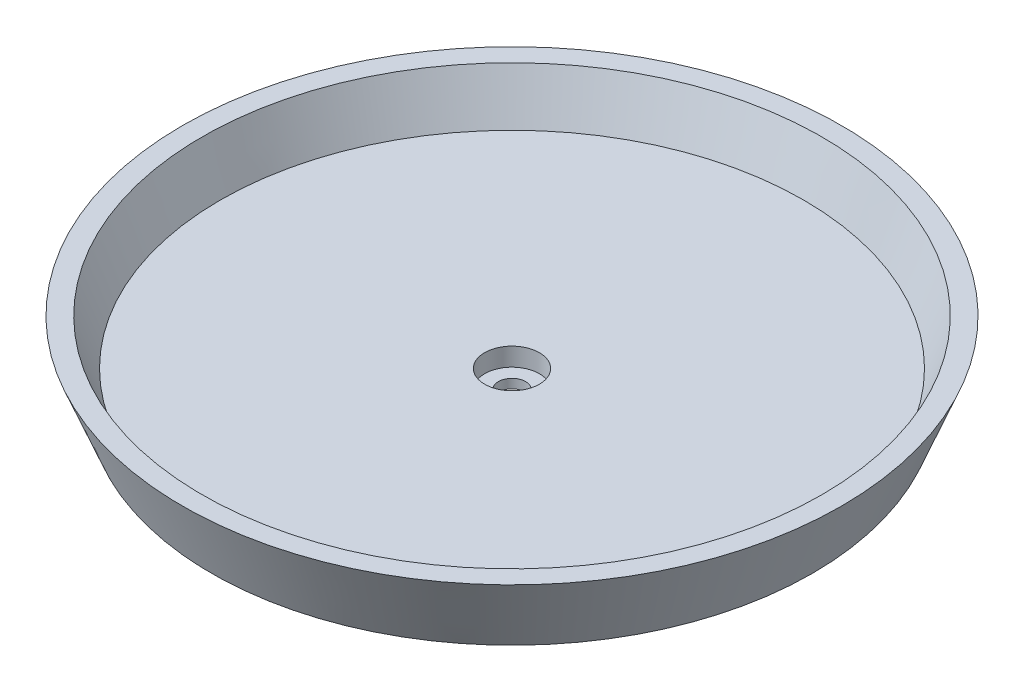
SolidWorks part; units mm, degrees
ref_plane "前视基准面" through (0, 0, 0) normal (0, 0, 1) x (1, 0, 0)
ref_plane "上视基准面" through (0, 0, 0) normal (0, 1, 0) x (1, 0, 0)
ref_plane "右视基准面" through (0, 0, 0) normal (1, 0, 0) x (0, 0, -1)
sketch "草图1" plane through (0, 0, 0) normal (0, 0, 1) x (1, 0, 0)
  line L0 (-50.5774, 13.4762) -> (-48.5774, 8.4762)
  line L1 (-48.5774, 8.4762) -> (17.4226, 8.4762)
  line L2 (-48.5774, 8.4762) -> (-48.5774, 5.4762)
  line L3 (-48.5774, 5.4762) -> (17.4226, 5.4762)
  line L4 (17.4226, 8.4762) -> (17.4226, 5.4762)
  line L5 (17.4226, 5.4762) -> (-50.5774, 5.4762)
  line L6 (17.4226, 5.4762) -> (17.4226, 13.4762)
  line L7 (17.4226, 13.4762) -> (-50.5774, 13.4762)
  line L8 (-50.5774, 5.4762) -> (-50.5774, 13.4762)
  line L9 (-53.0274, 14.2161) -> (-47.3215, -0.0487)
  line L10 (-50.5774, 13.4762) -> (-55.2334, 13.4762)
  line L11 (-53.0274, 14.2161) -> (-52.6195, 13.4762)
  line L13 (17.4226, 5.4762) -> (-16.5774, 5.4762)
  line L14 (17.4226, 5.4762) -> (17.4226, 13.4762)
  line L15 (17.4226, 13.4762) -> (-16.5774, 13.4762)
  line L16 (-16.5774, 5.4762) -> (-16.5774, 13.4762)
  line L17 (-16.5774, 8.4762) -> (-19.5774, 8.4762)
  line L18 (-16.5774, 8.4762) -> (-16.5774, 6.4762)
  line L19 (-16.5774, 6.4762) -> (-19.5774, 6.4762)
  line L20 (-19.5774, 8.4762) -> (-19.5774, 6.4762)
  line L21 (-16.5774, 5.4762) -> (-18.0774, 5.4762)
  line L22 (-16.5774, 5.4762) -> (-16.5774, 6.4762)
  line L23 (-16.5774, 6.4762) -> (-18.0774, 6.4762)
  line L24 (-18.0774, 5.4762) -> (-18.0774, 6.4762)
  dimension "D1" = 66
  dimension "D2" = 3
  dimension "D3" = 8
  dimension "D4" = 68
  dimension "D5" = 2
  dimension "D6" = 3
  dimension "D7" = 2
revolve "旋转1" add sketch "草图1" angle 360 about L16 region at (-49.658, 8.7091, 0) region at (-51.2954, 11.6811, 0) region at (-33.8189, 6.9592, 0)
